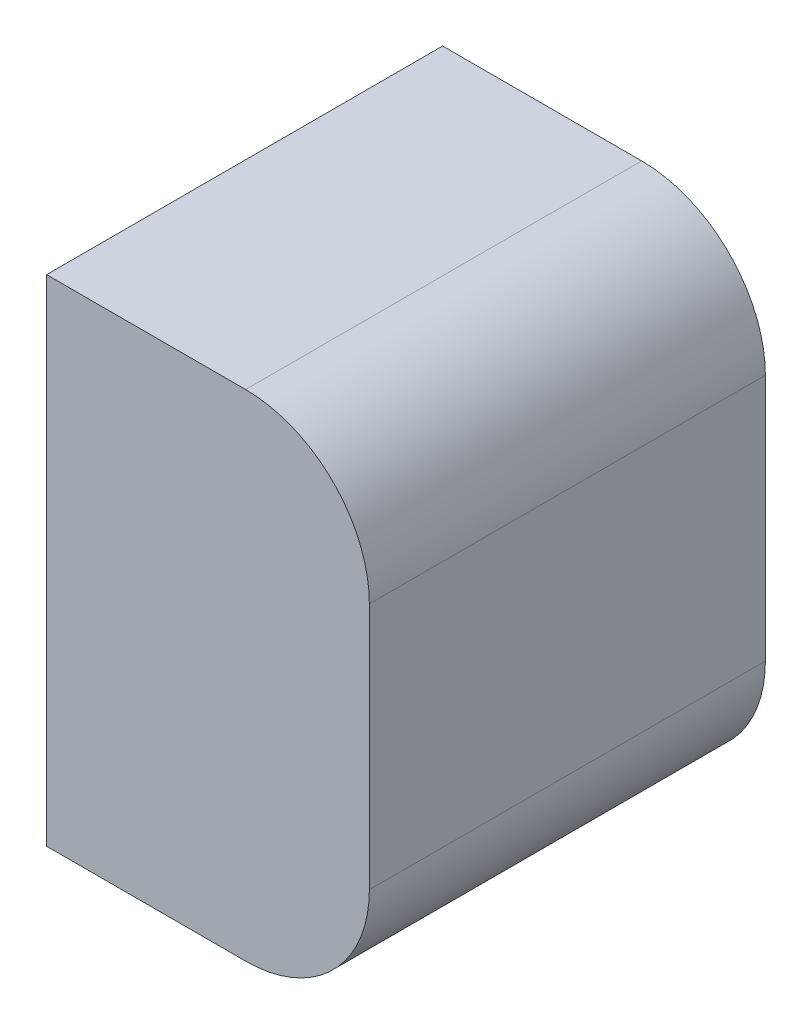
SolidWorks part; units mm, degrees
ref_plane "Front Plane" through (0, 0, 0) normal (0, 0, 1) x (1, 0, 0)
ref_plane "Top Plane" through (0, 0, 0) normal (0, 1, 0) x (1, 0, 0)
ref_plane "Right Plane" through (0, 0, 0) normal (1, 0, 0) x (0, 0, -1)
sketch "Sketch1" plane through (0, 0, 0) normal (0, 0, 1) x (1, 0, 0)
  line L0 (0.95, -6.25) -> (0.95, 6.25)
  line L1 (0.95, -6.25) -> (-0.95, -6.25)
  line L2 (0.95, 6.25) -> (-0.95, 6.25)
  line L3 (-0.95, -6.25) -> (-0.95, 6.25)
  line L4 (0.95, -6.25) -> (-0.95, 6.25) construction
  line L5 (0.95, 6.25) -> (-0.95, -6.25) construction
  line L6 (0.95, 6.25) -> (4.075, 6.25)
  line L7 (7.2, 3.125) -> (7.2, -3.125)
  line L8 (4.075, -6.25) -> (0.95, -6.25)
  circle A0 centre (4.075, 3.125) radius 3.125
  circle A1 centre (4.075, -3.125) radius 3.125
  point P1 (0, 0)
  point P14 (4.075, 3.1153)
  point P15 (0, 0)
  dimension "D3" = 6.25
  dimension "D1" = 1.9
  dimension "D2" = 12.5
extrude "Boss-Extrude1" add sketch "Sketch1" along normal blind 10 contours A0 | A0 L6 L0 | A1 L7 A0 | A1 | A1 A0 L0 | A1 L0 L8 | L3 L1 L0 L2 region at (0, 0, 0) region at (1.648, -5.552, 0) region at (1.648, 0, 0) region at (4.075, -3.125, 0) region at (1.648, 5.552, 0) region at (4.075, 3.125, 0) region at (6.502, 0, 0)
